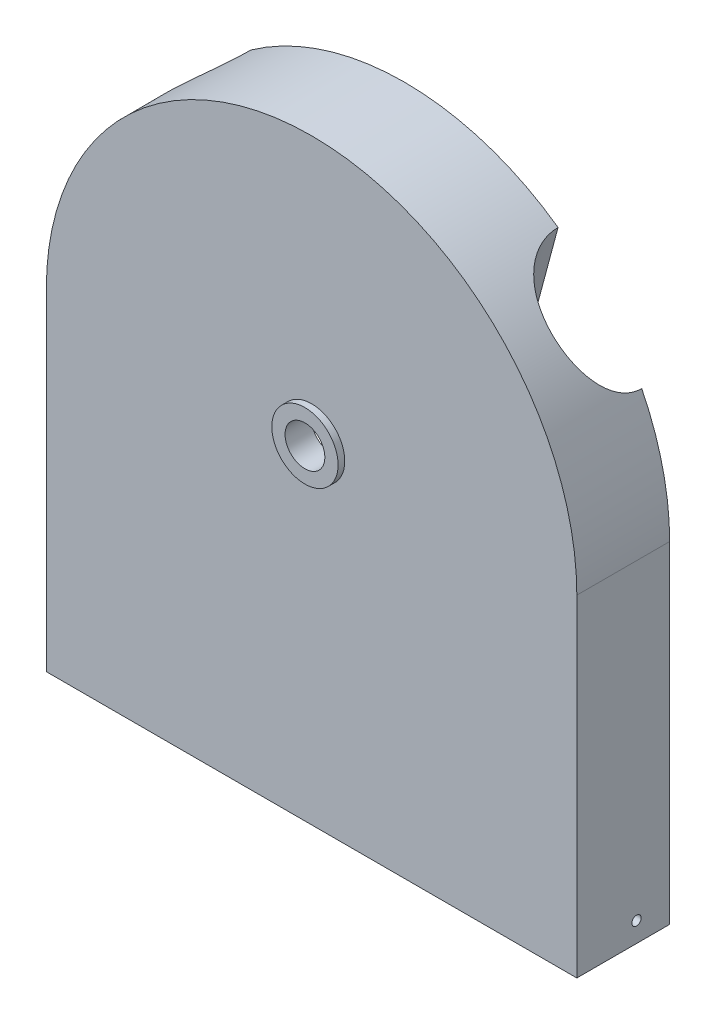
SolidWorks part; units mm, degrees
material "PE Low/Medium Density"
ref_plane "Plano frontal" through (0, 0, 0) normal (0, 0, 1) x (1, 0, 0)
ref_plane "Plano superior" through (0, 0, 0) normal (0, 1, 0) x (1, 0, 0)
ref_plane "Plano direito" through (0, 0, 0) normal (1, 0, 0) x (0, 0, -1)
sketch "Sketch2" plane through (0, 0, 0) normal (0, 0, 1) x (1, 0, 0)
  line L0 (-200, 0) -> (200, 0)
  line L1 (200, 0) -> (200, 250)
  line L3 (-200, 250) -> (-200, 0)
  arc A0 (200, 250) -> (-200, 250) centre (0, 250) ccw
  dimension "D1" = 400
  dimension "D2" = 250
extrude "Boss-Extrude4" add sketch "Sketch2" along normal mid plane 140
sketch "Sketch4" plane through (0, 0, 70) normal (0, 0, 1) x (1, 0, 0)
  circle A0 centre (0, 250) radius 25
  circle A1 centre (0, 250) radius 15
  dimension "D2" = 30
  dimension "D3" = 50
  dimension "D1" = 250
hole_wizard "Ø1.0mm Dowel Hole1" positions "3DSketch4" profile "Sketch7" hole size "Ø1.0" standard "ISO" end condition through all
sketch3d "3DSketch4"
  point P0 (0, 250, 70)
sketch "Sketch7" plane through (0, 250, 70) normal (1, 0, 0) x (0, -1, 0)
  line L0 (0, 0) -> (0, 140)
  line L1 (0, 140) -> (15, 140)
  line L2 (15, 140) -> (15, 0)
  line L5 (15, 0) -> (0, 0)
  line L11 (0, -6.35) -> (0, 107.95) construction
  dimension "Thru Hole Dia." = 30
  dimension "Thru Hole Depth" = 140
extrude "Boss-Extrude5" add sketch "Sketch4" along normal blind 5
sketch "Sketch13" plane through (0, 0, 0) normal (1, 0, 0) x (0, 0, -1)
  line L0 (0, 0) -> (0, 450)
  dimension "D1" = 450
extrude "Cut-Extrude4" cut sketch "Sketch13" against normal through all and the other way through all flip side to cut
sketch "Sketch14" plane through (0, 0, 0) normal (0, 0, -1) x (-1, 0, 0)
  line L0 (-185, 45) -> (-185, 200)
  line L2 (185, 200) -> (185, 45)
  line L8 (-200, 0) -> (200, 0) construction
  line L12 (-50, 420) -> (-50, 356.3309)
  line L13 (50, 420) -> (50, 356.3309)
  line L15 (0, 77) -> (0, -77) construction
  line L17 (-185, 45) -> (-178.3013, 20)
  line L18 (185, 45) -> (178.3013, 20)
  line L19 (-173.8807, 229.6159) -> (-88.4662, 327.3303)
  line L20 (173.8807, 229.6159) -> (88.4662, 327.3303)
  line L21 (-178.3013, 20) -> (-178.3013, 0)
  line L23 (-200, 0) -> (200, 0) construction
  line L24 (178.3013, 20) -> (178.3013, 0)
  line L25 (-178.3013, 0) -> (178.3013, 0)
  arc A1 (-185, 200) -> (-173.8807, 229.6159) centre (-140, 200) cw
  arc A2 (185, 200) -> (173.8807, 229.6159) centre (140, 200) ccw
  arc A3 (-50, 420) -> (50, 420) centre (0, 367.5) cw
  arc A4 (88.4662, 327.3303) -> (50, 356.3309) centre (0, 250) ccw
  arc A5 (-50, 356.3309) -> (-88.4662, 327.3303) centre (0, 250) ccw
  dimension "D1" = 280
  dimension "D3" = 200
  dimension "D6" = 72.5
  dimension "D7" = 117.5
  dimension "D2" = 370
  dimension "D4" = 20
  dimension "D5" = 50
  dimension "D8" = 165
  dimension "D9" = 45
extrude "Cut-Extrude5" cut sketch "Sketch14" against normal blind 55
hole_wizard "M8x1.0 Tapped Hole1" positions "Sketch19" profile "Sketch18" tap size "M8x1.0" standard "ISO"
sketch "Sketch19" plane through (-200, 0, 0) normal (-1, 0, 0) x (0, 0, 1)
  line L0 (70, 0) -> (0, 0) construction
  point P0 (25, 15)
  dimension "D1" = 15
  dimension "D4" = 25
sketch "Sketch18" plane through (-200, 15, 25) normal (0, 1, 0) x (0, 0, 1)
  line L0 (0, 0) -> (0, 13.103)
  line L1 (0, 13.103) -> (3.5, 11)
  line L2 (3.5, 11) -> (3.5, 0)
  line L5 (3.5, 0) -> (0, 0)
  line L10 (0, 13.103) -> (-3.5, 11) construction
  line L11 (0, -6.35) -> (0, 107.95) construction
  dimension "Tap Drill Dia." = 7
  dimension "Tap Drill Depth" = 11
  dimension "Drill Angle" = 118
cosmetic thread "Hole Thread4" parameters "D1"=16, "D2"=8
mirror "Mirror2" about plane through (0, 0, 0) normal (1, 0, 0) of "M8x1.0 Tapped Hole1"
cosmetic thread "Hole Thread5" parameters "D1"=16, "D2"=8
hole_wizard "Ø10.0mm Dowel Hole1" positions "Sketch20" profile "Sketch21" hole size "Ø10.0" standard "ISO"
sketch "Sketch20" plane through (0, 0, 0) normal (0, 0, -1) x (-1, 0, 0)
  line L0 (-200, 0) -> (-200, 250) construction
  line L1 (-200, 0) -> (-178.3013, 0) construction
  line L2 (-50, 420) -> (-50, 356.3309) construction
  point P0 (-185, 265)
  point P2 (-70, 370)
  point P4 (-70, 407.5)
  dimension "D1" = 15
  dimension "D2" = 265
  dimension "D3" = 120
  dimension "D4" = 37.5
  dimension "D5" = 20
sketch "Sketch21" plane through (185, 265, 0) normal (1, 0, 0) x (0, 1, 0)
  line L0 (0, 0) -> (0, 50)
  line L1 (0, 50) -> (5, 45)
  line L2 (5, 45) -> (5, 0)
  line L5 (5, 0) -> (0, 0)
  line L10 (0, 50) -> (-5, 45) construction
  line L11 (0, -6.35) -> (0, 107.95) construction
  dimension "Hole Dia." = 10
  dimension "Hole Depth" = 45
  dimension "Drill Angle" = 90
mirror "Mirror3" about plane through (0, 0, 0) normal (1, 0, 0) of "Ø10.0mm Dowel Hole1"
ref_plane "Plane1" through (-114.2638, 426.4383, 0) normal (-0.2588, 0.9659, 0) x (0, 0, -1)
sketch "Sketch22" plane through (-114.2638, 426.4383, 0) normal (-0.2588, 0.9659, 0) x (0, 0, -1)
  circle A0 centre (0, 45) radius 40
  point P2 (0, 0)
  dimension "D1" = 80
  dimension "D2" = 45
extrude "Cut-Extrude6" cut sketch "Sketch22" against normal up to surface (418.7058 mm away) up to face at (0, 0, 31.25)
mirror "Mirror4" about plane through (0, 0, 0) normal (1, 0, 0) of "Cut-Extrude6"
